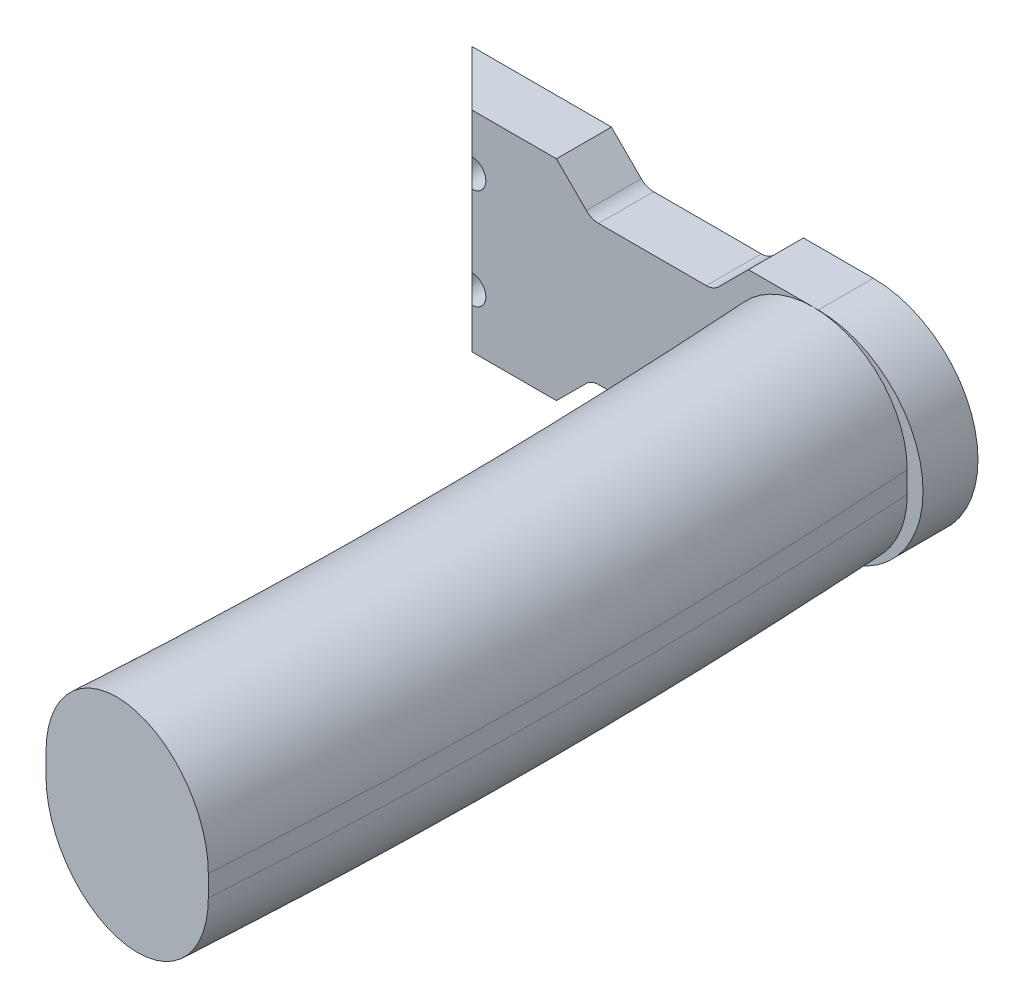
SolidWorks part; units mm, degrees
ref_plane "Front Plane" through (0, 0, 0) normal (0, 0, 1) x (1, 0, 0)
ref_plane "Top Plane" through (0, 0, 0) normal (0, 1, 0) x (1, 0, 0)
ref_plane "Right Plane" through (0, 0, 0) normal (1, 0, 0) x (0, 0, -1)
sketch "Sketch1" plane through (0, 0, 0) normal (0, 0, 1) x (1, 0, 0)
  line L0 (0, -19.05) -> (0, 19.05)
  line L1 (0, 19.05) -> (25.4, 19.05)
  line L2 (33.0651, 12.7) -> (52.6599, 12.7)
  line L3 (52.6599, -12.7) -> (33.0651, -12.7)
  line L4 (25.4, -19.05) -> (0, -19.05)
  line L5 (0, 0) -> (82.125, 0) construction
  line L6 (25.4, 19.05) -> (30.8201, 13.6299)
  line L7 (30.8201, -13.6299) -> (25.4, -19.05)
  line L8 (54.9049, -13.6299) -> (60.325, -19.05)
  line L9 (54.9049, 13.6299) -> (60.325, 19.05)
  line L10 (73.025, 19.05) -> (60.325, 19.05)
  line L11 (73.025, -19.05) -> (60.325, -19.05)
  arc A0 (73.025, -19.05) -> (73.025, 19.05) centre (73.025, 0) ccw
  arc A1 (33.0651, -12.7) -> (30.8201, -13.6299) centre (33.0651, -15.875) ccw
  arc A2 (33.0651, 12.7) -> (30.8201, 13.6299) centre (33.0651, 15.875) cw
  arc A3 (54.9049, -13.6299) -> (52.6599, -12.7) centre (52.6599, -15.875) ccw
  arc A4 (54.9049, 13.6299) -> (52.6599, 12.7) centre (52.6599, 15.875) cw
  point P11 (0, 0)
  point P18 (0, 0)
  point P24 (53.975, -12.7)
  dimension "D5" = 45
  dimension "D8" = 38.1
  dimension "D13" = 3.175
  dimension "D14" = 3.175
  dimension "D15" = 3.175
  dimension "D16" = 3.175
  dimension "D1" = 38.1
  dimension "D2" = 45
  dimension "D3" = 25.4
  dimension "D4" = 25.4
  dimension "D6" = 45
  dimension "D7" = 45
  dimension "D9" = 12.7
  dimension "D10" = 12.7
  dimension "D11" = 6.35
  dimension "D12" = 34.925
extrude "Boss-Extrude1" add sketch "Sketch1" along normal blind 10
chamfer "Chamfer1" distance 10 angle 45 1 edges at (0, 0, 10)
hole_wizard "1/4-20 Tapped Hole1" positions "Sketch3" profile "Sketch2" tap size "1/4-20" standard "ANSI Inch"
sketch "Sketch3" plane through (0, 0, 0) normal (0, 0, -1) x (-1, 0, 0)
  line L0 (-10, 9.144) -> (-10, -9.144) construction
  line L2 (-10, 19.05) -> (-10, -19.05) construction
  line L3 (-10, 0) -> (0, 0) construction
  point P0 (-10, -9.144)
  point P2 (-10, 9.144)
  point P14 (0, 0)
  dimension "D1" = 18.288
sketch "Sketch2" plane through (10, -9.144, 0) normal (1, 0, 0) x (0, 1, 0)
  line L0 (0, 0) -> (0, 16.51)
  line L1 (0, 16.51) -> (2.5527, 16.51)
  line L2 (2.5527, 16.51) -> (2.5527, 0)
  line L5 (2.5527, 0) -> (0, 0)
  line L10 (0, 16.51) -> (-2.5527, 16.51) construction
  line L11 (0, -6.35) -> (0, 107.95) construction
  dimension "Tap Drill Dia." = 5.1054
  dimension "Tap Drill Depth" = 16.51
  dimension "Drill Angle" = 180
cosmetic thread "Hole Thread1" parameters "D1"=10, "D2"=6.35
cosmetic thread "Hole Thread2" parameters "D1"=10, "D2"=6.35
sketch "Sketch5" plane through (0, 0, 10) normal (0, 0, 1) x (1, 0, 0)
  line L0 (60.325, -19.05) -> (73.025, -19.05) construction
  line L1 (73.025, 19.05) -> (60.325, 19.05) construction
  line L2 (89.2025, -1.9256) -> (89.2025, 1.9256)
  line L3 (54.9536, -1.9256) -> (54.9536, 1.9256)
  arc A1 (89.2025, 1.9256) -> (54.9536, 1.9256) centre (72.078, 1.9256) ccw
  arc A2 (54.9536, -1.9256) -> (89.2025, -1.9256) centre (72.078, -1.9256) ccw
sketch "Sketch8" plane through (0, 0, 0) normal (0, 1, 0) x (1, 0, 0)
  line L0 (88.2812, -10) -> (88.2812, -137) construction
  arc A0 (88.2812, -10) -> (88.2812, -137) centre (-888.3591, -73.5) cw
  point P4 (88.2812, -10)
  dimension "D1" = 127
  dimension "D2" = 0
sweep "Sweep1" add profiles "Sketch5" path "Sketch8"
